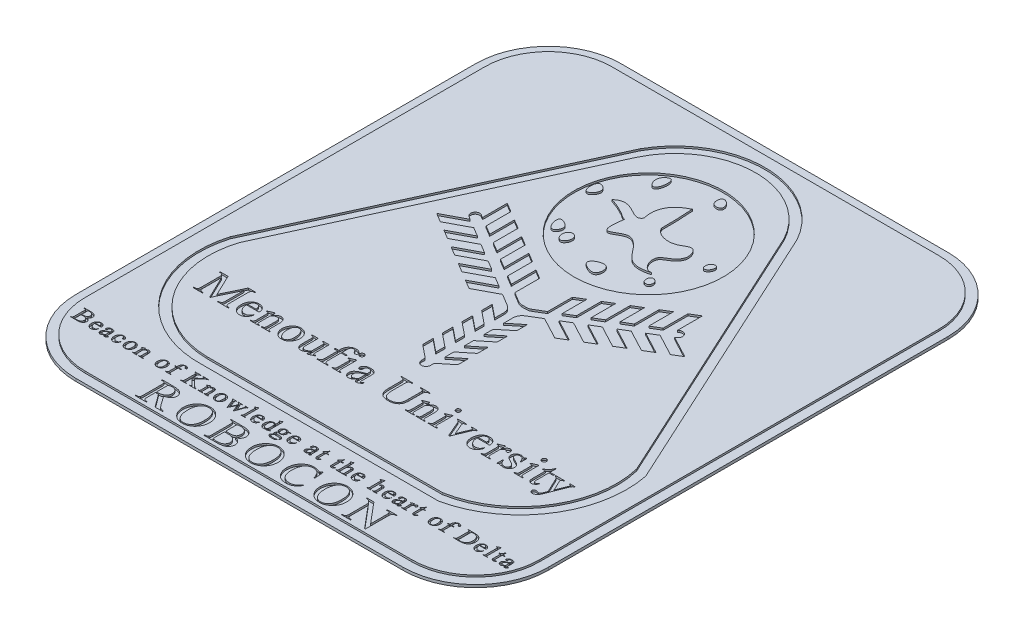
SolidWorks part; units mm, degrees
material "Maple"
ref_plane "Front Plane" through (0, 0, 0) normal (0, 0, 1) x (1, 0, 0)
ref_plane "Top Plane" through (0, 0, 0) normal (0, 1, 0) x (1, 0, 0)
ref_plane "Right Plane" through (0, 0, 0) normal (1, 0, 0) x (0, 0, -1)
sketch "Sketch1" plane through (0, 0, 0) normal (0, 1, 0) x (1, 0, 0)
  line L0 (22.3333, 28.3083) -> (111.6667, 28.3083) construction
  line L1 (-130, -150) -> (130, -150)
  line L2 (-130, -150) -> (-130, 150)
  line L3 (-130, 150) -> (130, 150)
  line L4 (130, -150) -> (130, 150)
  line L5 (-130, -150) -> (130, 150) construction
  line L6 (-130, 150) -> (130, -150) construction
  dimension "D1" = 260
  dimension "D2" = 300
extrude "Boss-Extrude1" add sketch "Sketch1" against normal blind 2.5 contours L4 L3 L2 L1
fillet "Fillet1" radius 40 4 edges at (130, -1.25, -150) (-130, -1.25, -150) (-130, -1.25, 150) (130, -1.25, 150)
sketch "Sketch3" plane through (0, 0, 0) normal (0, 1, 0) x (1, 0, 0)
  line L4 (-90, 150) -> (90, 150) construction
  line L5 (130, -110) -> (130, 110) construction
  line L6 (-43.2285, 113.6157) -> (-114.026, -41.006)
  line L7 (-39.9524, 108.9134) -> (-108.6551, -41.1333)
  line L8 (39.2289, 110.4804) -> (108.4679, -39.8529)
  line L9 (43.2629, 113.6739) -> (114.4365, -40.8598)
  line L10 (-63.3447, -104.5679) -> (66.3562, -104.5679)
  line L11 (-60.4019, -109.7043) -> (69.299, -109.7043)
  line L12 (3.6212, 7.463) -> (8.9484, 10.6671)
  line L13 (56.8594, 33.7077) -> (56.1819, 33.3003)
  line L14 (2.4054, -1.8718) -> (2.4054, -6.964)
  line L15 (-2.5443, -47.241) -> (-2.5443, -45.2105)
  line L16 (-4.9672, 2.4129) -> (-11.6385, 6.4255)
  line L17 (-55.3351, 38.4834) -> (-53.7697, 37.5419)
  line L18 (-1.1937, 6.7477) -> (1.0442, 6.7477)
  line L19 (53.6308, 37.5419) -> (53.6308, 51.1676)
  line L20 (53.6308, 51.1676) -> (48.6506, 48.1722)
  line L21 (48.6506, 48.1722) -> (48.6506, 34.5465)
  line L22 (53.6308, 51.1676) -> (8.9484, 24.2928) construction
  line L23 (43.7052, 45.1978) -> (43.7052, 31.572)
  line L24 (43.7052, 45.1978) -> (38.725, 42.2023)
  line L25 (38.725, 42.2023) -> (38.725, 28.5766)
  line L26 (33.7797, 25.6022) -> (33.7797, 39.2279)
  line L27 (33.7797, 39.2279) -> (28.7995, 36.2325)
  line L28 (28.7995, 36.2325) -> (28.7995, 22.6068)
  line L29 (23.8542, 19.6323) -> (23.8542, 33.2581)
  line L30 (23.8542, 33.2581) -> (18.874, 30.2626)
  line L31 (18.874, 30.2626) -> (18.874, 16.6369)
  line L32 (13.9286, 13.6625) -> (13.9286, 27.2882)
  line L33 (13.9286, 27.2882) -> (8.9484, 24.2928)
  line L34 (8.9484, 24.2928) -> (8.9484, 10.6671)
  line L35 (57.7046, 37.1041) -> (8.6183, 7.5805) construction
  line L36 (63.2382, 23.9186) -> (51.2017, 30.3049)
  line L37 (68.2184, 26.914) -> (63.2382, 23.9186)
  line L38 (56.1819, 33.3003) -> (68.2184, 26.914)
  line L39 (53.3127, 17.9488) -> (41.2762, 24.335)
  line L40 (58.2929, 20.9442) -> (53.3127, 17.9488)
  line L41 (58.2929, 20.9442) -> (46.2564, 27.3304)
  line L42 (43.3871, 11.9789) -> (31.3507, 18.3652)
  line L43 (48.3673, 14.9744) -> (43.3871, 11.9789)
  line L44 (36.3309, 21.3606) -> (48.3673, 14.9744)
  line L45 (33.4616, 6.0091) -> (21.4251, 12.3953)
  line L46 (38.4418, 9.0045) -> (33.4616, 6.0091)
  line L47 (26.4053, 15.3907) -> (38.4418, 9.0045)
  line L48 (23.5361, 0.0392) -> (11.4996, 6.4255)
  line L49 (28.5163, 3.0347) -> (23.5361, 0.0392)
  line L50 (16.4798, 9.4209) -> (28.5163, 3.0347)
  line L51 (-0.0695, -49.7159) -> (-0.0695, -6.8678) construction
  line L52 (-9.0873, 24.2928) -> (-9.0873, 10.6671)
  line L53 (-14.0676, 27.2882) -> (-9.0873, 24.2928)
  line L54 (-14.0676, 13.6625) -> (-14.0676, 27.2882)
  line L55 (-19.0129, 30.2626) -> (-19.0129, 16.6369)
  line L56 (-23.9931, 33.2581) -> (-19.0129, 30.2626)
  line L57 (-23.9931, 19.6323) -> (-23.9931, 33.2581)
  line L58 (-28.9384, 36.2325) -> (-28.9384, 22.6068)
  line L59 (-33.9186, 39.2279) -> (-28.9384, 36.2325)
  line L60 (-33.9186, 25.6022) -> (-33.9186, 39.2279)
  line L61 (-43.8442, 45.1978) -> (-43.8442, 31.572)
  line L62 (-43.8442, 45.1978) -> (-38.8639, 42.2023)
  line L63 (-38.8639, 42.2023) -> (-38.8639, 28.5766)
  line L64 (-48.7895, 48.1722) -> (-48.7895, 34.5465)
  line L65 (-53.7697, 51.1676) -> (-48.7895, 48.1722)
  line L66 (-53.7697, 37.5419) -> (-53.7697, 51.1676)
  line L67 (-58.4318, 20.9442) -> (-46.3953, 27.3304)
  line L68 (-58.4318, 20.9442) -> (-53.4516, 17.9488)
  line L69 (-53.4516, 17.9488) -> (-41.4151, 24.335)
  line L70 (-63.3771, 23.9186) -> (-51.3406, 30.3049)
  line L71 (-68.3573, 26.914) -> (-63.3771, 23.9186)
  line L72 (-56.3209, 33.3003) -> (-68.3573, 26.914)
  line L73 (-53.4516, 17.9488) -> (-41.4151, 24.335)
  line L74 (-43.526, 11.9789) -> (-31.4896, 18.3652)
  line L75 (-48.5063, 14.9744) -> (-43.526, 11.9789)
  line L76 (-36.4698, 21.3606) -> (-48.5063, 14.9744)
  line L77 (-33.6005, 6.0091) -> (-21.564, 12.3953)
  line L78 (-38.5807, 9.0045) -> (-33.6005, 6.0091)
  line L79 (-26.5443, 15.3907) -> (-38.5807, 9.0045)
  line L80 (-23.675, 0.0392) -> (-11.6385, 6.4255)
  line L81 (-28.6552, 3.0347) -> (-23.675, 0.0392)
  line L82 (-16.6187, 9.4209) -> (-28.6552, 3.0347)
  line L83 (9.6018, -34.3973) -> (9.6018, -1.1508) construction
  line L84 (2.4054, -6.964) -> (9.6018, -1.1508)
  line L85 (9.6018, -1.1508) -> (9.6018, -6.9624)
  line L86 (9.6018, -6.9624) -> (2.4054, -12.7756)
  line L87 (2.4054, -17.7756) -> (9.6018, -11.9624)
  line L88 (9.6018, -11.9624) -> (9.6018, -17.774)
  line L89 (9.6018, -17.774) -> (2.4054, -23.5872)
  line L90 (2.4054, -28.5872) -> (9.6018, -22.774)
  line L91 (9.6018, -22.774) -> (9.6018, -28.5857)
  line L92 (9.6018, -28.5857) -> (2.4054, -34.3989)
  line L93 (2.4054, -34.3989) -> (2.4054, -39.3989)
  line L94 (2.4054, -39.3989) -> (9.6018, -33.5857)
  line L95 (2.4054, -45.2105) -> (9.6018, -39.3973)
  line L96 (9.6018, -39.3973) -> (9.6018, -33.5857)
  line L97 (48.6506, 48.1722) -> (43.7052, 45.1978) construction
  line L98 (38.725, 42.2023) -> (33.7797, 39.2279) construction
  line L99 (28.7995, 36.2325) -> (23.8542, 33.2581) construction
  line L100 (18.874, 30.2626) -> (13.9286, 27.2882) construction
  line L101 (9.6018, -6.9624) -> (9.6018, -11.9624) construction
  line L102 (9.6018, -17.774) -> (9.6018, -22.774) construction
  line L103 (9.6018, -28.5857) -> (9.6018, -33.5857) construction
  line L104 (-2.5443, -45.2105) -> (-9.7408, -39.3973)
  line L105 (-9.7408, -39.3973) -> (-9.7408, -33.5857)
  line L106 (-2.5443, -39.3989) -> (-9.7408, -33.5857)
  line L107 (-9.7408, -28.5857) -> (-2.5443, -34.3989)
  line L108 (-9.7408, -22.774) -> (-9.7408, -28.5857)
  line L109 (-2.5443, -28.5872) -> (-9.7408, -22.774)
  line L110 (-9.7408, -17.774) -> (-2.5443, -23.5872)
  line L111 (-9.7408, -11.9624) -> (-9.7408, -17.774)
  line L112 (-2.5443, -17.7756) -> (-9.7408, -11.9624)
  line L113 (-9.7408, -6.9624) -> (-2.5443, -12.7756)
  line L114 (-9.7408, -1.1508) -> (-9.7408, -6.9624)
  line L115 (-2.5443, -6.964) -> (-9.7408, -1.1508)
  line L116 (53.6308, 37.5419) -> (54.3082, 37.9493)
  line L117 (43.7052, 31.572) -> (48.6506, 34.5465)
  line L118 (33.7797, 25.6022) -> (38.725, 28.5766)
  line L119 (23.8542, 19.6323) -> (28.7995, 22.6068)
  line L120 (13.9286, 13.6625) -> (18.874, 16.6369)
  line L121 (11.4996, 6.4255) -> (4.8283, 2.4129)
  line L122 (21.4251, 12.3953) -> (16.4798, 9.4209)
  line L123 (31.3507, 18.3652) -> (26.4053, 15.3907)
  line L124 (41.2762, 24.335) -> (36.3309, 21.3606)
  line L125 (51.2017, 30.3049) -> (46.2564, 27.3304)
  line L126 (-2.5443, -6.964) -> (-2.5443, -1.8718)
  line L127 (-2.5443, -17.7756) -> (-2.5443, -12.7756)
  line L128 (2.4054, -23.5872) -> (2.4054, -28.5872)
  line L129 (2.4054, -12.7756) -> (2.4054, -17.7756)
  line L130 (-9.0873, 10.6671) -> (-3.751, 7.4575)
  line L131 (-16.6187, 9.4209) -> (-21.564, 12.3953)
  line L132 (-19.0129, 16.6369) -> (-14.0676, 13.6625)
  line L133 (-26.5443, 15.3907) -> (-31.4896, 18.3652)
  line L134 (-28.9384, 22.6068) -> (-23.9931, 19.6323)
  line L135 (-36.4698, 21.3606) -> (-41.4151, 24.335)
  line L136 (2.4054, -34.3989) -> (2.4054, -39.3989)
  line L137 (-2.5443, -28.5872) -> (-2.5443, -23.5872)
  line L138 (-2.5443, -39.3989) -> (-2.5443, -34.3989)
  line L139 (2.4054, -45.2105) -> (2.4054, -47.241)
  line L140 (-38.8639, 28.5766) -> (-33.9186, 25.6022)
  line L141 (-46.3953, 27.3304) -> (-51.3406, 30.3049)
  line L142 (-48.7895, 34.5465) -> (-43.8442, 31.572)
  line L143 (-56.3209, 33.3003) -> (-57.8863, 34.2418)
  line L144 (-90, -150) -> (90, -150) construction
  line L145 (-130, -110) -> (-130, 110) construction
  line L146 (-90, 150) -> (90, 150)
  line L147 (130, -110) -> (130, 110)
  line L148 (-90, -150) -> (90, -150)
  line L149 (-130, -110) -> (-130, 110)
  line L150 (-125, -110) -> (-125, 110)
  line L151 (-90, 145) -> (90, 145)
  line L152 (125, -110) -> (125, 110)
  line L153 (-90, -145) -> (90, -145)
  arc A0 (-39.9524, 108.9134) -> (39.2289, 110.4804) centre (0.0333, 89.7364) cw
  arc A1 (-43.2285, 113.6157) -> (43.2629, 113.6739) centre (0.0333, 89.7364) cw
  arc A2 (-108.6551, -41.1333) -> (-63.3447, -104.5679) centre (-62.5123, -56.0737) ccw
  arc A3 (-114.026, -41.006) -> (-60.4019, -109.7043) centre (-62.5123, -56.0737) ccw
  arc A4 (66.3562, -104.5679) -> (108.4679, -39.8529) centre (56.837, -52.3144) ccw
  arc A5 (114.4365, -40.8598) -> (69.299, -109.7043) centre (56.837, -52.3144) cw
  circle A6 centre (-0.2776, 75.5104) radius 41.0998
  arc A7 (-55.3351, 38.4834) -> (-57.8863, 34.2418) centre (-56.6107, 36.3626) ccw
  arc A8 (54.3082, 37.9493) -> (56.8594, 33.7077) centre (55.5838, 35.8285) cw
  arc A9 (-2.5443, -47.241) -> (2.4054, -47.241) centre (-0.0695, -47.241) ccw
  arc A10 (-1.1937, 6.7477) -> (-3.751, 7.4575) centre (-1.1937, 11.7093) cw
  arc A11 (1.0442, 6.7477) -> (3.6212, 7.463) centre (1.0442, 11.7477) ccw
  arc A12 (2.4054, -1.8718) -> (4.8283, 2.4129) centre (7.4054, -1.8718) cw
  arc A13 (-2.5443, -1.8718) -> (-4.9672, 2.4129) centre (-7.5443, -1.8718) ccw
  arc A14 (-90, 150) -> (-130, 110) centre (-90, 110) ccw construction
  arc A15 (130, 110) -> (90, 150) centre (90, 110) ccw construction
  arc A16 (90, -150) -> (130, -110) centre (90, -110) ccw construction
  arc A17 (-130, -110) -> (-90, -150) centre (-90, -110) ccw construction
  arc A18 (-90, 150) -> (-130, 110) centre (-90, 110) ccw
  arc A19 (130, 110) -> (90, 150) centre (90, 110) ccw
  arc A20 (90, -150) -> (130, -110) centre (90, -110) ccw
  arc A21 (-130, -110) -> (-90, -150) centre (-90, -110) ccw
  arc A22 (-90, 145) -> (-125, 110) centre (-90, 110) ccw
  arc A23 (125, 110) -> (90, 145) centre (90, 110) ccw
  arc A24 (90, -145) -> (125, -110) centre (90, -110) ccw
  arc A25 (-125, -110) -> (-90, -145) centre (-90, -110) ccw
  spline S0 degree 2 poles (-0.0272, 99.2445) (-11.8579, 93.4431) (-9.0873, 81.7765) knots 0 0 0 1 1 1
  spline S1 degree 3 poles (-9.0873, 81.7765) (-10.6133, 78.664) (-17.8225, 83.8677) (-23.2987, 84.7128) (-26.6385, 81.7765) knots 0 0 0 0 0.441289 1 1 1 1
  spline S2 degree 2 poles (-26.6385, 81.7765) (-19.8463, 79.6452) (-14.0873, 75.5104) knots 0 0 0 1 1 1
  spline S3 degree 3 poles (-14.0873, 75.5104) (-13.1966, 77.9485) (-16.5801, 63.1434) (-8.8307, 67.6099) (-4.648, 70.012) (5.4008, 63.6842) (6.3671, 53.997) (18.874, 57.7844) knots 0 0 0 0 0.215321 0.292078 0.438757 0.525213 1 1 1 1
  spline S4 degree 3 poles (18.874, 57.7844) (14.5696, 57.2028) (10.8101, 65.9069) (17.9998, 69.6865) (23.0394, 73.88) (19.3543, 82.4427) (13.8619, 78.1441) (7.5061, 76.6525) (2.033, 78.6069) (0.5392, 81.7765) knots 0 0 0 0 0.241765 0.306206 0.473676 0.587577 0.696013 0.8006 1 1 1 1
  spline S5 degree 2 poles (0.5392, 81.7765) (0.5779, 90.5164) (-0.0272, 99.2445) knots 0 0 0 1 1 1
  spline S6 degree 3 poles (4.91, 41.1901) (5.3787, 51.8157) (-6.7844, 45.9791) (-0.5698, 42.013) (4.91, 41.1901) (5.3787, 51.8157) (-6.7844, 45.9791) knots -0.64606 -0.440103 -0.268746 0 0.35394 0.559897 0.731254 1 1.35394 1.559897 1.731254 only from (3.5574, 48.3066) to (3.5574, 48.3066)
  spline S7 degree 3 poles (-33.891, 80.9224) (-33.7286, 84.5934) (-39.8453, 88.5234) (-39.325, 75.3515) (-33.891, 80.9224) (-33.7286, 84.5934) (-39.8453, 88.5234) knots -0.77389 -0.375029 -0.114458 0 0.22611 0.624971 0.885542 1 1.22611 1.624971 1.885542 only from (-34.0873, 83.8811) to (-34.0873, 83.8811)
  spline S8 degree 3 poles (-25.4063, 55.0677) (-28.4595, 57.7764) (-33.9702, 59.3803) (-30.331, 47.8679) (-25.4063, 55.0677) (-28.4595, 57.7764) (-33.9702, 59.3803) knots -0.857289 -0.456106 -0.211456 0 0.142711 0.543894 0.788544 1 1.142711 1.543894 1.788544 only from (-29.0873, 57.7844) to (-29.0873, 57.7844)
  spline S9 degree 3 poles (-21.1505, 46.2074) (-17.4519, 52.9188) (-22.2277, 55.9369) (-25.2651, 51.441) (-21.1505, 46.2074) (-17.4519, 52.9188) (-22.2277, 55.9369) knots -0.817014 -0.560112 -0.327942 0 0.182986 0.439888 0.672058 1 1.182986 1.439888 1.672058 only from (-19.0873, 53.1543) to (-19.0873, 53.1543)
  spline S10 degree 3 poles (24.822, 50.8078) (24.7938, 55.197) (20.3472, 56.0361) (20.3159, 50.7366) (24.822, 50.8078) (24.7938, 55.197) (20.3472, 56.0361) knots -0.799661 -0.481584 -0.28414 0 0.200339 0.518416 0.71586 1 1.200339 1.518416 1.71586 only from (23.874, 54.838) to (23.874, 54.838)
  spline S11 degree 3 poles (7.9923, 106.7791) (7.7615, 111.1559) (2.4973, 114.4625) (2.0973, 106.6113) (7.9923, 106.7791) (7.7615, 111.1559) (2.4973, 114.4625) knots -0.721331 -0.413284 -0.170773 0 0.278669 0.586716 0.829227 1 1.278669 1.586716 1.829227 only from (7.3682, 110.3462) to (7.3682, 110.3462)
  spline S12 degree 3 poles (-21.2253, 96.4323) (-18.5279, 103.6401) (-19.8509, 109.3827) (-26.1265, 104.4847) (-21.2253, 96.4323) (-18.5279, 103.6401) (-19.8509, 109.3827) knots -0.844749 -0.582537 -0.301871 0 0.155251 0.417463 0.698129 1 1.155251 1.417463 1.698129 only from (-19.0873, 104.7164) to (-19.0873, 104.7164)
  spline S13 degree 3 poles (34.462, 75.2884) (34.7053, 79.2494) (30.1694, 78.6028) (30.4926, 72.5949) (34.462, 75.2884) (34.7053, 79.2494) (30.1694, 78.6028) knots -0.804132 -0.472332 -0.245097 0 0.195868 0.527668 0.754903 1 1.195868 1.527668 1.754903 only from (33.874, 78.6197) to (33.874, 78.6197)
  line M18 (130, -110) -> (130, 110)
  arc M19 (130, 110) -> (90, 150) centre (90, 110) ccw
  line M20 (90, 150) -> (-90, 150)
  arc M21 (-90, 150) -> (-130, 110) centre (-90, 110) ccw
  line M22 (-130, 110) -> (-130, -110)
  arc M23 (-130, -110) -> (-90, -150) centre (-90, -110) ccw
  line M24 (-90, -150) -> (90, -150)
  arc M25 (90, -150) -> (130, -110) centre (90, -110) ccw
  dimension "D1" = 5
  dimension "D2" = 5
extrude "Cut-Extrude1" cut sketch "Sketch3" against normal blind 1 contours A5 L9 A1 L6 A3 L11 A4 L10 A2 L7 A0 L8 | A6 S13 S12 S11 S10 S9 S8 S7 S6 S5 S4 S3 S2 S1 S0 | A13 L126 L115 L114 L113 L127 L112 L111 L110 L137 L109 L108 L107 L138 L106 L105 L104 L15 A9 L139 L95 L96 L94 L93 L92 L91 L90 L128 L89 L88 L87 L129 L86 L85 L84 L14 A12 L121 L48 L49 L50 L122 L45 L46 L47 L123 L42 L43 L44 L124 L39 | A25 L150 A22 L151 A23 L152 A24 L153 M25 M18 M19 M20 M21 M22 M23 M24 region at (0.0023, 0, -135.7502) region at (7.16, 0, -7.61) region at (0, 0, -146.0301) region at (-40.2149, 0, -75.5104)
sketch "Sketch4" plane through (0, 0, 0) normal (0, 1, 0) x (1, 0, 0)
  line L0 (-100.2626, -75.5007) -> (100.2626, -75.5007) construction
  line L1 (-90, -150) -> (90, -150) construction
  line L2 (-100.2626, -142.9167) -> (100.2626, -142.9167) construction
  line L3 (-121.1118, -123.0921) -> (121.1118, -123.0921) construction
  text T0 "Menoufia University" font "Times New Roman" height 15
  text T1 "ROBOCON" font "Times New Roman" height 15
  text T2 "Beacon of Knowledge at the heart of Delta" font "Times New Roman" height 8
  point P2 (0, -75.5007)
  point P5 (0, -150)
  point P8 (0, -142.9167)
  point P13 (119.6924, -117.8646)
  point P14 (0, -123.0921)
extrude "Cut-Extrude2" cut sketch "Sketch4" against normal blind 1
